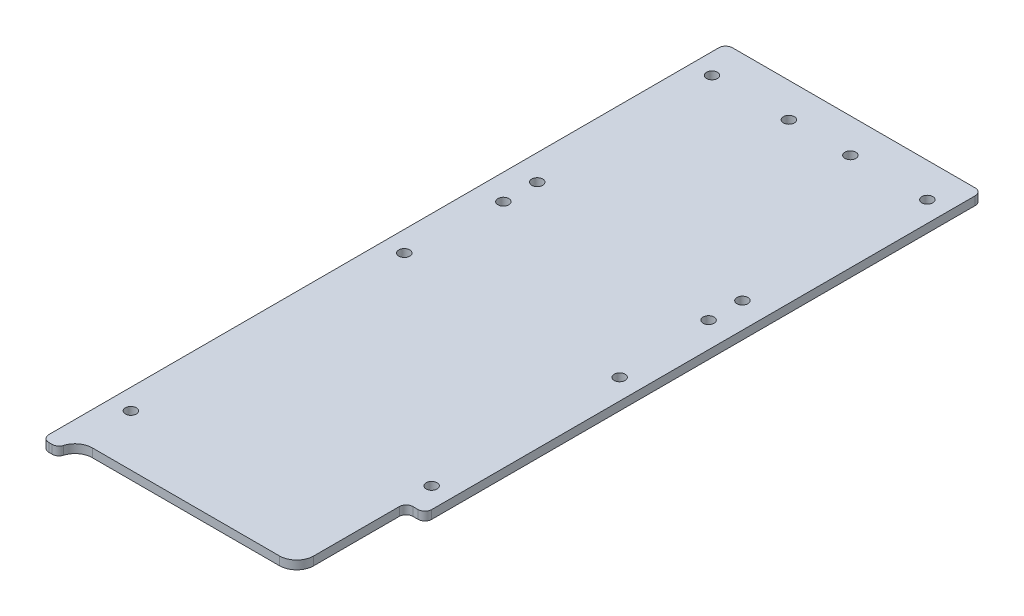
SolidWorks part; units mm, degrees
ref_plane "Front Plane" through (0, 0, 0) normal (0, 0, 1) x (1, 0, 0)
ref_plane "Top Plane" through (0, 0, 0) normal (0, 1, 0) x (1, 0, 0)
ref_plane "Right Plane" through (0, 0, 0) normal (1, 0, 0) x (0, 0, -1)
sketch "Sketch1" plane through (0, 0, 0) normal (0, 1, 0) x (1, 0, 0)
  line L0 (-39.9997, 0) -> (-39.9997, 114.3) construction
  line L1 (-47.625, 127) -> (47.625, 127)
  line L2 (-47.625, 127) -> (-47.625, -127)
  line L3 (-47.625, -127) -> (47.625, -127)
  line L4 (47.625, 127) -> (47.625, -127)
  line L5 (-47.625, 127) -> (47.625, -127) construction
  line L6 (-47.625, -127) -> (47.625, 127) construction
  line L7 (0, 0) -> (0, 127) construction
  line L8 (-39.9997, 0) -> (-39.9997, -101.6) construction
  line L9 (-39.9997, 0) -> (0, 0) construction
  line L10 (-41.275, -127) -> (-41.275, -120.65)
  line L11 (-41.275, -120.65) -> (41.275, -120.65)
  line L12 (41.275, -120.65) -> (41.275, -127)
  line L13 (-39.9997, 114.3) -> (-11.4247, 114.3) construction
  line L14 (39.9997, 114.3) -> (11.4247, 114.3) construction
  circle A0 centre (-39.9997, 114.3) radius 2.032
  circle A1 centre (-39.9997, 0) radius 2.032
  circle A2 centre (-39.9997, -101.6) radius 2.032
  circle A3 centre (39.9997, -101.6) radius 2.032
  circle A4 centre (39.9997, 0) radius 2.032
  circle A5 centre (39.9997, 114.3) radius 2.032
  circle A6 centre (-11.4247, 114.3) radius 2.032
  circle A7 centre (11.4247, 114.3) radius 2.032
  circle A8 centre (-39.9997, -69.85) radius 2.032
  circle A9 centre (39.9997, -69.85) radius 2.032
  point P0 (0, 0)
  dimension "D4" = 4.064
  dimension "D10" = 28.575
  dimension "D1" = 95.25
  dimension "D2" = 254
  dimension "D3" = 7.6253
  dimension "D5" = 12.7
  dimension "D6" = 25.4
  dimension "D7" = 6.35
  dimension "D8" = 6.35
  dimension "D9" = 6.35
  dimension "D11" = 69.85
extrude "Boss-Extrude1" add sketch "Sketch1" along normal blind 3.175 contours L4 L1 L2 L3 A4 A0 A1 A2 A3 A5 | A8 | A3 region at (0, 0, -2.6944) region at (39.9997, 0, 101.6) region at (-39.9997, 0, 69.85)
fillet "Fillet1" radius 2.54 4 edges at (-47.625, 1.5875, -127) (47.625, 1.5875, -127) (47.625, 1.5875, 127) (-47.625, 1.5875, 127)
fillet "Fillet2" radius 2.54 2 edges at (41.275, 1.5875, 127) (-41.275, 1.5875, 127)
fillet "Fillet3" radius 6.35 2 edges at (41.275, 1.5875, 120.65) (-41.275, 1.5875, 120.65)
sketch "Sketch2" plane through (0, 0, 0) normal (0, -1, 0) x (1, 0, 0)
  line L0 (41.9106, 131.8831) -> (41.9106, 109.8659) construction
  line L1 (41.9106, 109.8659) -> (41.9106, 106.3879) construction
  line L2 (41.9106, 83.271) -> (41.9106, 82.5325) construction
  line L3 (41.9106, 82.5325) -> (41.9106, 81.2514) construction
  line L4 (41.9106, 83.271) -> (41.9106, 106.3879) construction
  line L5 (41.9106, 131.8831) -> (41.9106, 109.8659)
  line L6 (41.9106, 109.8659) -> (41.9106, 106.3879)
  line L7 (41.9106, 83.271) -> (41.9106, 82.5325)
  line L8 (41.9106, 82.5325) -> (41.9106, 81.2514)
  line L9 (41.9106, 83.271) -> (41.9106, 106.3879)
  line L10 (41.9106, 81.2514) -> (47.625, 81.2514)
  line L11 (47.625, -124.46) -> (47.625, 124.46) construction
  line L12 (41.9106, 131.8831) -> (47.625, 131.8831)
  line L13 (47.625, 131.8831) -> (47.625, 81.2514)
  line L14 (40.6406, 79.9814) -> (48.895, 79.9814)
  line L15 (48.895, 133.1531) -> (48.895, 79.9814)
  line L16 (40.6406, 133.1531) -> (48.895, 133.1531)
  line L17 (40.6406, 133.1531) -> (40.6406, 109.8659)
  line L18 (40.6406, 109.8659) -> (40.6406, 106.3879)
  line L19 (40.6406, 83.271) -> (40.6406, 106.3879)
  line L20 (40.6406, 83.271) -> (40.6406, 82.5325)
  line L21 (40.6406, 82.5325) -> (40.6406, 79.9814)
  arc M7 (43.815, 127) -> (41.3809, 125.1857) centre (43.815, 124.46) ccw
  arc M8 (41.3809, 125.1857) -> (35.2956, 120.65) centre (35.2956, 127) cw
  line M18 (47.625, -124.46) -> (47.625, 124.46)
  dimension "D1" = 1.27
extrude "Cut-Extrude1" cut sketch "Sketch2" against normal through all contours L20 L21 L14 L10 L8 L7 L9 L19 M18 | L19 L9 L6 L5 L17 L18 M7 M8 | L13 L10 L8 L7 L9 L6 L5 L12 region at (41.6757, 0, 99.9796)
fillet "Fillet4" radius 6.35 1 edges at (40.6406, 1.5875, 123.5717)
fillet "Fillet5" radius 2.54 2 edges at (47.625, 1.5875, 79.9814) (40.6406, 1.5875, 79.9814)
sketch "Sketch3" plane through (0, 0, 0) normal (0, -1, 0) x (1, 0, 0)
  line L0 (-36.3099, -49.7791) -> (-39.9167, -49.7791) construction
  line L1 (-40.4247, -49.276) -> (-40.4247, -45.7043) construction
  line L2 (-35.8019, -45.7043) -> (-35.8019, -49.276) construction
  line L3 (-39.9167, -45.2013) -> (-36.3099, -45.2013) construction
  line L4 (-36.3099, -37.2027) -> (-39.9167, -37.2027) construction
  line L5 (-35.8019, -33.1279) -> (-35.8019, -36.6996) construction
  line L6 (-40.4247, -36.6996) -> (-40.4247, -33.1279) construction
  line L7 (-39.9167, -32.6249) -> (-36.3099, -32.6249) construction
  line L8 (36.2833, -32.6249) -> (39.8901, -32.6249) construction
  line L9 (40.3981, -33.1279) -> (40.3981, -36.6996) construction
  line L10 (39.8901, -37.2027) -> (36.2833, -37.2027) construction
  line L11 (35.7753, -36.6996) -> (35.7753, -33.1279) construction
  line L12 (36.2833, -45.2013) -> (39.8901, -45.2013) construction
  line L13 (35.7753, -49.276) -> (35.7753, -45.7043) construction
  line L14 (40.3981, -45.7043) -> (40.3981, -49.276) construction
  line L15 (39.8901, -49.7791) -> (36.2833, -49.7791) construction
  line L16 (-36.3099, -49.7791) -> (-39.9167, -49.7791)
  line L17 (-40.4247, -49.276) -> (-40.4247, -45.7043)
  line L18 (-35.8019, -45.7043) -> (-35.8019, -49.276)
  line L19 (-39.9167, -45.2013) -> (-36.3099, -45.2013)
  line L20 (-36.3099, -37.2027) -> (-39.9167, -37.2027)
  line L21 (-35.8019, -33.1279) -> (-35.8019, -36.6996)
  line L22 (-40.4247, -36.6996) -> (-40.4247, -33.1279)
  line L23 (-39.9167, -32.6249) -> (-36.3099, -32.6249)
  line L24 (36.2833, -32.6249) -> (39.8901, -32.6249)
  line L25 (40.3981, -33.1279) -> (40.3981, -36.6996)
  line L26 (39.8901, -37.2027) -> (36.2833, -37.2027)
  line L27 (35.7753, -36.6996) -> (35.7753, -33.1279)
  line L28 (36.2833, -45.2013) -> (39.8901, -45.2013)
  line L29 (35.7753, -49.276) -> (35.7753, -45.7043)
  line L30 (40.3981, -45.7043) -> (40.3981, -49.276)
  line L31 (39.8901, -49.7791) -> (36.2833, -49.7791)
  line L32 (-47.625, -25.836) -> (47.625, -25.836)
  line L33 (-47.625, -124.46) -> (-47.625, 124.46) construction
  line L34 (47.625, -124.46) -> (47.625, 77.4414) construction
  line L35 (0, -25.836) -> (0, -56.0686) construction
  line L38 (134.3609, -51.414) -> (184.1367, -51.414)
  line L39 (184.1367, -51.414) -> (184.1367, -43.4909)
  line L40 (184.1367, -43.4909) -> (182.3333, -43.4909)
  line L41 (181.8253, -42.9878) -> (181.8253, -39.4161)
  line L42 (182.3333, -38.9131) -> (184.1367, -38.9131)
  line L43 (184.1367, -38.9131) -> (184.1367, -30.9899)
  line L44 (184.1367, -30.9899) -> (134.3609, -30.9899)
  line L45 (134.3609, -30.9899) -> (133.3367, -32.0042)
  line L46 (133.3367, -32.0042) -> (132.3125, -30.9899)
  line L47 (132.3125, -30.9899) -> (70.8609, -30.9899)
  line L48 (70.8609, -30.9899) -> (69.8367, -32.0042)
  line L49 (69.8367, -32.0042) -> (68.8125, -30.9899)
  line L50 (68.8125, -30.9899) -> (7.3609, -30.9899)
  line L51 (7.3609, -30.9899) -> (6.3367, -32.0042)
  line L52 (6.3367, -32.0042) -> (5.3125, -30.9899)
  line L53 (5.3125, -30.9899) -> (-56.1391, -30.9899)
  line L54 (-56.1391, -30.9899) -> (-57.1633, -32.0042)
  line L55 (-57.1633, -32.0042) -> (-58.1875, -30.9899)
  line L56 (-58.1875, -30.9899) -> (-119.6391, -30.9899)
  line L57 (-119.6391, -30.9899) -> (-120.6633, -32.0042)
  line L58 (-120.6633, -32.0042) -> (-121.6875, -30.9899)
  line L59 (-121.6875, -30.9899) -> (-184.1633, -30.9899)
  line L60 (-184.1633, -30.9899) -> (-184.1633, -51.414)
  line L61 (-184.1633, -51.414) -> (-121.6875, -51.414)
  line L62 (-121.6875, -51.414) -> (-120.6633, -50.3998)
  line L63 (-120.6633, -50.3998) -> (-119.6391, -51.414)
  line L64 (-119.6391, -51.414) -> (-58.1875, -51.414)
  line L65 (-58.1875, -51.414) -> (-57.1633, -50.3998)
  line L66 (-57.1633, -50.3998) -> (-56.1391, -51.414)
  line L67 (-56.1391, -51.414) -> (5.3125, -51.414)
  line L68 (5.3125, -51.414) -> (6.3367, -50.3998)
  line L69 (6.3367, -50.3998) -> (7.3609, -51.414)
  line L70 (7.3609, -51.414) -> (68.8125, -51.414)
  line L71 (68.8125, -51.414) -> (69.8367, -50.3998)
  line L72 (69.8367, -50.3998) -> (70.8609, -51.414)
  line L73 (70.8609, -51.414) -> (132.3125, -51.414)
  line L74 (132.3125, -51.414) -> (133.3367, -50.3998)
  line L75 (133.3367, -50.3998) -> (134.3609, -51.414)
  line L76 (134.3609, -51.414) -> (184.1367, -51.414)
  line L77 (184.1367, -51.414) -> (184.1367, -43.4909)
  line L78 (184.1367, -43.4909) -> (182.3333, -43.4909)
  line L79 (181.8253, -42.9878) -> (181.8253, -39.4161)
  line L80 (182.3333, -38.9131) -> (184.1367, -38.9131)
  line L81 (184.1367, -38.9131) -> (184.1367, -30.9899)
  line L82 (184.1367, -30.9899) -> (134.3609, -30.9899)
  line L83 (134.3609, -30.9899) -> (133.3367, -32.0042)
  line L84 (133.3367, -32.0042) -> (132.3125, -30.9899)
  line L85 (132.3125, -30.9899) -> (70.8609, -30.9899)
  line L86 (70.8609, -30.9899) -> (69.8367, -32.0042)
  line L87 (69.8367, -32.0042) -> (68.8125, -30.9899)
  line L88 (68.8125, -30.9899) -> (7.3609, -30.9899)
  line L89 (7.3609, -30.9899) -> (6.3367, -32.0042)
  line L90 (6.3367, -32.0042) -> (5.3125, -30.9899)
  line L91 (5.3125, -30.9899) -> (-56.1391, -30.9899)
  line L92 (-56.1391, -30.9899) -> (-57.1633, -32.0042)
  line L93 (-57.1633, -32.0042) -> (-58.1875, -30.9899)
  line L94 (-58.1875, -30.9899) -> (-119.6391, -30.9899)
  line L95 (-119.6391, -30.9899) -> (-120.6633, -32.0042)
  line L96 (-120.6633, -32.0042) -> (-121.6875, -30.9899)
  line L97 (-121.6875, -30.9899) -> (-184.1633, -30.9899)
  line L98 (-184.1633, -30.9899) -> (-184.1633, -51.414)
  line L99 (-184.1633, -51.414) -> (-121.6875, -51.414)
  line L100 (-121.6875, -51.414) -> (-120.6633, -50.3998)
  line L101 (-120.6633, -50.3998) -> (-119.6391, -51.414)
  line L102 (-119.6391, -51.414) -> (-58.1875, -51.414)
  line L103 (-58.1875, -51.414) -> (-57.1633, -50.3998)
  line L104 (-57.1633, -50.3998) -> (-56.1391, -51.414)
  line L105 (-56.1391, -51.414) -> (5.3125, -51.414)
  line L106 (5.3125, -51.414) -> (6.3367, -50.3998)
  line L107 (6.3367, -50.3998) -> (7.3609, -51.414)
  line L108 (7.3609, -51.414) -> (68.8125, -51.414)
  line L109 (68.8125, -51.414) -> (69.8367, -50.3998)
  line L110 (69.8367, -50.3998) -> (70.8609, -51.414)
  line L111 (70.8609, -51.414) -> (132.3125, -51.414)
  line L112 (132.3125, -51.414) -> (133.3367, -50.3998)
  line L113 (133.3367, -50.3998) -> (134.3609, -51.414)
  line L1362 (-40.4247, -34.9138) -> (-35.8019, -34.9138)
  line L1857 (-38.1133, -32.6249) -> (-38.1133, -37.2027)
  line L1858 (-38.1133, -45.2013) -> (-38.1133, -49.7791)
  line L1859 (-40.4247, -47.4902) -> (-35.8019, -47.4902)
  circle A0 centre (-38.1133, -34.9138) radius 2.032
  circle A1 centre (-38.1133, -47.4902) radius 2.032
  circle A2 centre (38.1133, -47.4902) radius 2.032
  circle A3 centre (38.1133, -34.9138) radius 2.032
  ellipse E0 centre (-39.9167, -45.7043) end of major axis (-39.4087, -45.7043) minor radius 0.5031 (-39.9167, -45.2013) -> (-40.4247, -45.7043) ccw construction
  ellipse E1 centre (-39.9167, -49.276) end of major axis (-39.4087, -49.276) minor radius 0.5031 (-40.4247, -49.276) -> (-39.9167, -49.7791) ccw construction
  ellipse E2 centre (182.3333, -42.9878) end of major axis (182.8413, -42.9878) minor radius 0.5031 (181.8253, -42.9878) -> (182.3333, -43.4909) ccw
  ellipse E3 centre (182.3333, -39.4161) end of major axis (182.8413, -39.4161) minor radius 0.5031 (182.3333, -38.9131) -> (181.8253, -39.4161) ccw
  ellipse E4 centre (182.3333, -42.9878) end of major axis (182.8413, -42.9878) minor radius 0.5031 (181.8253, -42.9878) -> (182.3333, -43.4909) ccw
  ellipse E5 centre (182.3333, -39.4161) end of major axis (182.8413, -39.4161) minor radius 0.5031 (182.3333, -38.9131) -> (181.8253, -39.4161) ccw
  ellipse E6 centre (-36.3099, -49.276) end of major axis (-35.8019, -49.276) minor radius 0.5031 (-36.3099, -49.7791) -> (-35.8019, -49.276) ccw construction
  ellipse E7 centre (-36.3099, -45.7043) end of major axis (-35.8019, -45.7043) minor radius 0.5031 (-35.8019, -45.7043) -> (-36.3099, -45.2013) ccw construction
  ellipse E8 centre (-39.9167, -36.6996) end of major axis (-39.4087, -36.6996) minor radius 0.5031 (-40.4247, -36.6996) -> (-39.9167, -37.2027) ccw construction
  ellipse E9 centre (-36.3099, -36.6996) end of major axis (-35.8019, -36.6996) minor radius 0.5031 (-36.3099, -37.2027) -> (-35.8019, -36.6996) ccw construction
  ellipse E10 centre (-36.3099, -33.1279) end of major axis (-35.8019, -33.1279) minor radius 0.5031 (-35.8019, -33.1279) -> (-36.3099, -32.6249) ccw construction
  ellipse E11 centre (-39.9167, -33.1279) end of major axis (-39.4087, -33.1279) minor radius 0.5031 (-39.9167, -32.6249) -> (-40.4247, -33.1279) ccw construction
  ellipse E12 centre (39.8901, -33.1279) end of major axis (40.3981, -33.1279) minor radius 0.5031 (40.3981, -33.1279) -> (39.8901, -32.6249) ccw construction
  ellipse E13 centre (36.2833, -33.1279) end of major axis (36.7913, -33.1279) minor radius 0.5031 (36.2833, -32.6249) -> (35.7753, -33.1279) ccw construction
  ellipse E14 centre (39.8901, -36.6996) end of major axis (40.3981, -36.6996) minor radius 0.5031 (39.8901, -37.2027) -> (40.3981, -36.6996) ccw construction
  ellipse E15 centre (36.2833, -36.6996) end of major axis (36.7913, -36.6996) minor radius 0.5031 (35.7753, -36.6996) -> (36.2833, -37.2027) ccw construction
  ellipse E16 centre (36.2833, -45.7043) end of major axis (36.7913, -45.7043) minor radius 0.5031 (36.2833, -45.2013) -> (35.7753, -45.7043) ccw construction
  ellipse E17 centre (36.2833, -49.276) end of major axis (36.7913, -49.276) minor radius 0.5031 (35.7753, -49.276) -> (36.2833, -49.7791) ccw construction
  ellipse E18 centre (39.8901, -45.7043) end of major axis (40.3981, -45.7043) minor radius 0.5031 (40.3981, -45.7043) -> (39.8901, -45.2013) ccw construction
  ellipse E19 centre (39.8901, -49.276) end of major axis (40.3981, -49.276) minor radius 0.5031 (39.8901, -49.7791) -> (40.3981, -49.276) ccw construction
  ellipse E20 centre (-39.9167, -45.7043) end of major axis (-39.4087, -45.7043) minor radius 0.5031 (-39.9167, -45.2013) -> (-40.4247, -45.7043) ccw
  ellipse E21 centre (-39.9167, -49.276) end of major axis (-39.4087, -49.276) minor radius 0.5031 (-40.4247, -49.276) -> (-39.9167, -49.7791) ccw
  ellipse E22 centre (-36.3099, -49.276) end of major axis (-35.8019, -49.276) minor radius 0.5031 (-36.3099, -49.7791) -> (-35.8019, -49.276) ccw
  ellipse E23 centre (-36.3099, -45.7043) end of major axis (-35.8019, -45.7043) minor radius 0.5031 (-35.8019, -45.7043) -> (-36.3099, -45.2013) ccw
  ellipse E24 centre (-39.9167, -36.6996) end of major axis (-39.4087, -36.6996) minor radius 0.5031 (-40.4247, -36.6996) -> (-39.9167, -37.2027) ccw
  ellipse E25 centre (-36.3099, -36.6996) end of major axis (-35.8019, -36.6996) minor radius 0.5031 (-36.3099, -37.2027) -> (-35.8019, -36.6996) ccw
  ellipse E26 centre (-36.3099, -33.1279) end of major axis (-35.8019, -33.1279) minor radius 0.5031 (-35.8019, -33.1279) -> (-36.3099, -32.6249) ccw
  ellipse E27 centre (-39.9167, -33.1279) end of major axis (-39.4087, -33.1279) minor radius 0.5031 (-39.9167, -32.6249) -> (-40.4247, -33.1279) ccw
  ellipse E28 centre (39.8901, -33.1279) end of major axis (40.3981, -33.1279) minor radius 0.5031 (40.3981, -33.1279) -> (39.8901, -32.6249) ccw
  ellipse E29 centre (36.2833, -33.1279) end of major axis (36.7913, -33.1279) minor radius 0.5031 (36.2833, -32.6249) -> (35.7753, -33.1279) ccw
  ellipse E30 centre (39.8901, -36.6996) end of major axis (40.3981, -36.6996) minor radius 0.5031 (39.8901, -37.2027) -> (40.3981, -36.6996) ccw
  ellipse E31 centre (36.2833, -36.6996) end of major axis (36.7913, -36.6996) minor radius 0.5031 (35.7753, -36.6996) -> (36.2833, -37.2027) ccw
  ellipse E32 centre (36.2833, -45.7043) end of major axis (36.7913, -45.7043) minor radius 0.5031 (36.2833, -45.2013) -> (35.7753, -45.7043) ccw
  ellipse E33 centre (36.2833, -49.276) end of major axis (36.7913, -49.276) minor radius 0.5031 (35.7753, -49.276) -> (36.2833, -49.7791) ccw
  ellipse E34 centre (39.8901, -45.7043) end of major axis (40.3981, -45.7043) minor radius 0.5031 (40.3981, -45.7043) -> (39.8901, -45.2013) ccw
  ellipse E35 centre (39.8901, -49.276) end of major axis (40.3981, -49.276) minor radius 0.5031 (39.8901, -49.7791) -> (40.3981, -49.276) ccw
  dimension "D2" = 4.064
  dimension "D1" = 0
extrude "Cut-Extrude2" cut sketch "Sketch3" against normal through all contours A0 | A1 | A2 | A3
